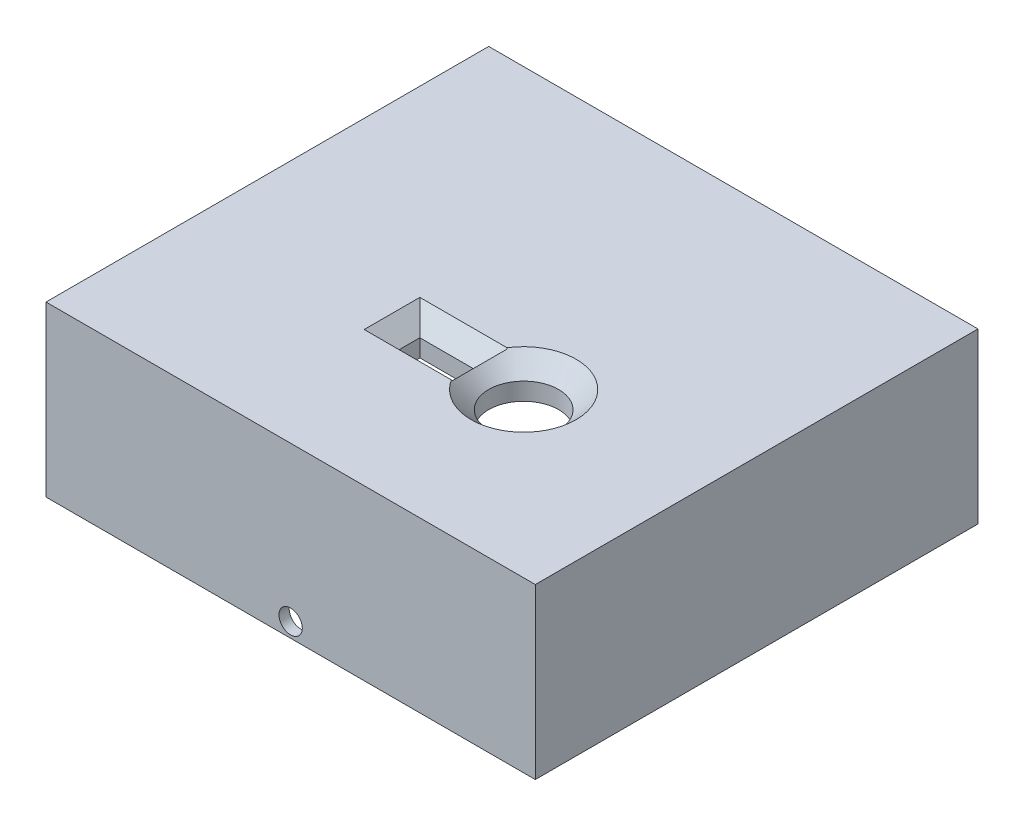
SolidWorks part; units mm, degrees
ref_plane "Front Plane" through (0, 0, 0) normal (0, 0, 1) x (1, 0, 0)
ref_plane "Top Plane" through (0, 0, 0) normal (0, 1, 0) x (1, 0, 0)
ref_plane "Right Plane" through (0, 0, 0) normal (1, 0, 0) x (0, 0, -1)
sketch "Sketch1" plane through (0, 17.2172, 0) normal (0, 1, 0) x (1, 0, 0)
  line L0 (-29.7596, 17.8556) -> (-29.7596, -18.1444) construction
  line L1 (-31.7596, 21.8556) -> (52.2403, 21.8556)
  line L2 (-31.7596, 21.8556) -> (-31.7596, -54.1444)
  line L3 (-31.7596, -54.1444) -> (52.2403, -54.1444)
  line L4 (52.2403, 21.8556) -> (52.2403, -54.1444)
  line L5 (49.2403, 19.8556) -> (-28.7596, 19.8556) construction
  line L6 (50.2403, 16.3556) -> (50.2403, -50.6443) construction
  line L7 (49.2403, -52.1444) -> (-28.7596, -52.1444) construction
  line L9 (11.8124, -24.3664) -> (2.6404, -24.3664)
  line L10 (11.8124, -24.3664) -> (11.8124, -27.9222)
  line L11 (11.8124, -27.9222) -> (2.6404, -27.9222)
  line L12 (2.6404, -24.3664) -> (2.6404, -27.9222)
  circle A0 centre (22.2403, -26.1444) radius 6
  dimension "D5" = 12
  dimension "D1" = 2
  dimension "D2" = 2
  dimension "D3" = 2
  dimension "D4" = 2
extrude "Boss-Extrude1" add sketch "Sketch1" along normal blind 2
sketch "Sketch2" plane through (0, 17.2172, 0) normal (0, -1, 0) x (1, 0, 0)
  line L0 (-30.0096, 52.3944) -> (-30.0096, -20.1056)
  line L1 (-31.7596, 54.1444) -> (52.2403, 54.1444)
  line L2 (-31.7596, 54.1444) -> (-31.7596, -21.8556)
  line L3 (-31.7596, -21.8556) -> (52.2403, -21.8556)
  line L4 (52.2403, 54.1444) -> (52.2403, -21.8556)
  line L5 (-30.0096, -20.1056) -> (50.4903, -20.1056)
  line L6 (50.4903, 52.3944) -> (50.4903, -20.1056)
  line L7 (-30.0096, 52.3944) -> (50.4903, 52.3944)
  dimension "D1" = 1.75
extrude "Boss-Extrude2" add sketch "Sketch2" along normal up to surface (27 mm away)
sketch "Sketch4" plane through (-31.7596, 0, 0) normal (-1, 0, 0) x (0, 0, 1)
  line L0 (-21.8556, 19.2172) -> (-21.8556, -9.7828) construction
  line L6 (40.0823, 17.2172) -> (24.2064, 17.2172)
  line L7 (40.0823, 17.2172) -> (40.0823, 9.7172)
  line L8 (40.0823, 9.7172) -> (24.2064, 9.7172)
  line L9 (24.2064, 17.2172) -> (24.2064, 9.7172)
  line L10 (-17.8556, -2.7828) -> (18.1444, -2.7828) construction
  circle A0 centre (-6.8556, 11.2172) radius 4
  point P7 (-6.8556, 7.2172)
  point P12 (0.1444, -2.7828)
  dimension "D1" = 8
  dimension "D2" = 10
  dimension "D3" = 15
extrude "Cut-Extrude1" cut sketch "Sketch4" against normal blind 5
sketch "Sketch5" plane through (0, 0, 54.1444) normal (0, 0, 1) x (1, 0, 0)
  circle A0 centre (10.2404, -7.2828) radius 2
  dimension "D1" = 4
extrude "Cut-Extrude2" cut sketch "Sketch5" against normal through all
sketch "Sketch6" plane through (0, 17.2172, 0) normal (0, -1, 0) x (1, 0, 0)
  line L10 (0.6404, 29.9222) -> (20.6486, 33.9844)
  line L11 (0.6404, 22.3664) -> (20.6486, 18.3043)
  line L12 (2.6404, 24.3664) -> (2.6404, 27.9222) construction
  line L13 (11.8124, 24.3664) -> (2.6404, 24.3664) construction
  line L14 (0.6404, 29.9222) -> (0.6404, 22.3664)
  line L15 (0.6404, 22.3664) -> (13.8124, 22.3664)
  line L16 (13.8124, 22.3664) -> (13.8124, 29.9222)
  line L17 (13.8124, 29.9222) -> (0.6404, 29.9222)
  line L18 (0.6404, 29.9222) -> (0.6404, 22.3664)
  line L19 (0.6404, 22.3664) -> (13.8124, 22.3664) construction
  line L20 (13.8124, 22.3664) -> (13.8124, 29.9222) construction
  line L21 (13.8124, 29.9222) -> (0.6404, 29.9222) construction
  line L22 (11.8124, 27.9222) -> (11.8124, 24.3664) construction
  line L23 (2.6404, 27.9222) -> (11.8124, 27.9222) construction
  line L24 (2.6404, 24.3664) -> (2.6404, 27.9222)
  line L25 (11.8124, 24.3664) -> (2.6404, 24.3664)
  line L26 (11.8124, 27.9222) -> (11.8124, 24.3664)
  line L27 (2.6404, 27.9222) -> (11.8124, 27.9222)
  arc A0 (20.6486, 18.3043) -> (20.6486, 33.9844) centre (22.2403, 26.1444) ccw
  arc A2 (20.6486, 33.9844) -> (20.6486, 18.3043) centre (22.2403, 26.1444) ccw construction
  circle A3 centre (22.2403, 26.1444) radius 6 construction
  circle A4 centre (22.2403, 26.1444) radius 6
  dimension "D1" = 16
  dimension "D2" = 2
extrude "Boss-Extrude3" add sketch "Sketch6" along normal blind 4
chamfer "Chamfer1" distance 3 angle 45 5 edges at (7.2264, 19.2172, 24.3664) (11.8124, 19.2172, 26.1443) (7.2264, 19.2172, 27.9222) (22.2403, 19.2172, 32.1444) (2.6404, 19.2172, 26.1443)
chamfer "Chamfer2" distance 2 angle 45 2 edges at (-30.8846, 17.2172, 24.2064) (-30.8846, 17.2172, 40.0823)
